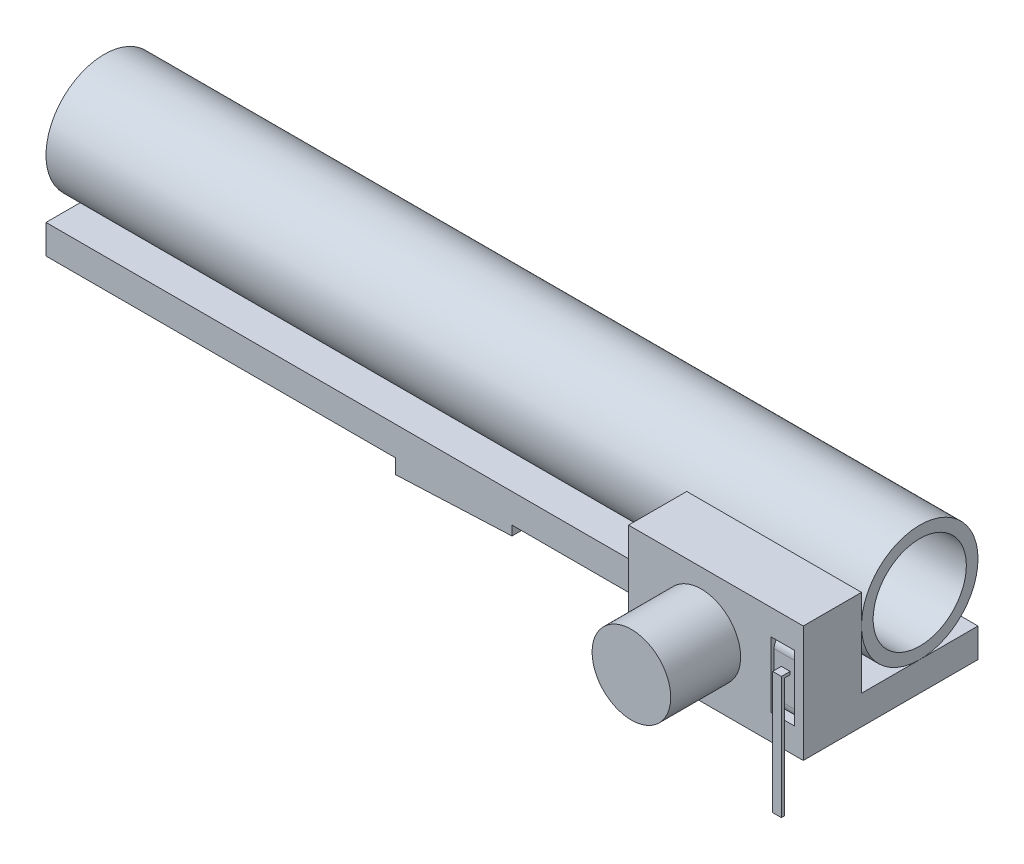
SolidWorks part; units mm, degrees
ref_plane "Front Plane" through (0, 0, 0) normal (0, 0, 1) x (1, 0, 0)
ref_plane "Top Plane" through (0, 0, 0) normal (0, 1, 0) x (1, 0, 0)
ref_plane "Right Plane" through (0, 0, 0) normal (1, 0, 0) x (0, 0, -1)
sketch "Sketch2" plane through (0, 0, 0) normal (1, 0, 0) x (0, 0, -1)
  line L0 (-25.4, 25.4) -> (-25.4, -25.4) construction
  line L1 (-25.4, -25.4) -> (25.4, -25.4) construction
  line L2 (25.4, -25.4) -> (25.4, 25.4) construction
  line L3 (25.4, 25.4) -> (-25.4, 25.4) construction
  point P2 (25.4, 0)
  point P5 (0, 25.4)
  dimension "D1" = 50.8
ref_plane "Plane1" through (0, 0, 0) normal (1, 0, 0) x (0, 0, -1)
sketch "Sketch3" plane through (0, 0, 0) normal (1, 0, 0) x (0, 0, -1)
  circle A0 centre (0, 0) radius 25.4
  dimension "D1" = 50.8
extrude "Boss-Extrude1" add sketch "Sketch3" against normal blind 355.6
shell "Shell1" thickness 5.08 removed face at (0, 0, -25.4)
sketch "Sketch4" plane through (0, 0, 0) normal (0, 0, 1) x (1, 0, 0)
  line L0 (-355.6, -25.4) -> (0, -25.4)
  line L2 (0, -27.94) -> (0, 27.94) construction
  line L3 (-355.6, -25.4) -> (0, -25.4) construction
  line L4 (-355.6, -25.4) -> (-355.6, -38.1)
  line L5 (-355.6, -38.1) -> (0, -38.1)
  line L6 (0, -38.1) -> (0, -25.4)
  dimension "D1" = 12.7
extrude "Boss-Extrude2" add sketch "Sketch4" along normal blind 25.4 and the other way blind 25.4 separate body
sketch "Sketch5" plane through (0, 0, 25.4) normal (0, 0, 1) x (1, 0, 0)
  line L1 (0, -38.1) -> (-76.2, -38.1)
  line L2 (0, -38.1) -> (0, 12.7)
  line L3 (0, 12.7) -> (-76.2, 12.7)
  line L4 (-76.2, -38.1) -> (-76.2, 12.7)
  line L8 (-355.6, -38.1) -> (0, -38.1) construction
  line L9 (0, -38.1) -> (0, -25.4) construction
  dimension "D1" = 76.2
  dimension "D2" = 50.8
extrude "Boss-Extrude3" add sketch "Sketch5" along normal blind 25.4
sketch "Sketch6" plane through (0, 0, 50.8) normal (0, 0, 1) x (1, 0, 0)
  line L1 (-3.81, -26.9875) -> (-13.97, -26.9875)
  line L2 (-3.81, -26.9875) -> (-3.81, 1.5875)
  line L3 (-3.81, 1.5875) -> (-13.97, 1.5875)
  line L4 (-13.97, -26.9875) -> (-13.97, 1.5875)
  line L5 (-3.81, 1.5875) -> (-3.81, 12.7) construction
  line L6 (0, 12.7) -> (-76.2, 12.7) construction
  line L7 (0, -38.1) -> (0, 12.7) construction
  line L8 (-3.81, -26.9875) -> (-3.81, -38.1) construction
  line L9 (-76.2, -38.1) -> (0, -38.1) construction
  dimension "D1" = 28.575
  dimension "D2" = 10.16
  dimension "D3" = 3.81
extrude "Cut-Extrude1" cut sketch "Sketch6" against normal blind 19.05
sketch "Sketch7" plane through (-13.97, 0, 0) normal (1, 0, 0) x (0, 0, -1)
  line L0 (-31.75, 1.5875) -> (-31.75, -26.9875) construction
  line L1 (-44.45, -26.9875) -> (-36.83, -26.9875)
  line L2 (-49.53, -21.9075) -> (-49.53, -3.4925)
  line L3 (-44.45, 1.5875) -> (-36.83, 1.5875)
  line L4 (-31.75, -21.9075) -> (-31.75, -3.4925)
  line L5 (-31.75, 1.5875) -> (-50.8, 1.5875) construction
  line L6 (-50.8, 1.5875) -> (-50.8, -26.9875) construction
  line L7 (-31.75, -26.9875) -> (-50.8, -26.9875) construction
  arc A0 (-36.83, -26.9875) -> (-31.75, -21.9075) centre (-36.83, -21.9075) ccw
  arc A1 (-44.45, -26.9875) -> (-49.53, -21.9075) centre (-44.45, -21.9075) cw
  arc A2 (-36.83, 1.5875) -> (-31.75, -3.4925) centre (-36.83, -3.4925) cw
  arc A3 (-49.53, -3.4925) -> (-44.45, 1.5875) centre (-44.45, -3.4925) cw
  point P14 (-50.8, -26.9875)
  dimension "D1" = 5.08
  dimension "D2" = 1.27
extrude "Boss-Extrude4" add sketch "Sketch7" along normal up to next
sketch "Sketch8" plane through (0, 0, 49.53) normal (0, 0, 1) x (1, 0, 0)
  line L0 (-3.81, -3.4925) -> (-13.97, -3.4925) construction
  line L1 (-10.795, -8.5725) -> (-6.985, -8.5725)
  line L2 (-10.795, -8.5725) -> (-10.795, -9.8425)
  line L3 (-10.795, -9.8425) -> (-6.985, -9.8425)
  line L4 (-6.985, -8.5725) -> (-6.985, -9.8425)
  point P6 (-8.89, -8.5725)
  point P7 (-8.89, -3.4925)
  dimension "D1" = 5.08
  dimension "D2" = 1.27
  dimension "D3" = 3.81
extrude "Boss-Extrude5" add sketch "Sketch8" along normal blind 2.54
sketch "Sketch10" plane through (0, 0, 52.07) normal (0, 0, 1) x (1, 0, 0)
  line L0 (-3.81, 1.5875) -> (-13.97, 1.5875) construction
  line L1 (-10.795, -8.5725) -> (-6.985, -8.5725)
  line L2 (-10.795, -8.5725) -> (-10.795, -61.9125)
  line L3 (-10.795, -61.9125) -> (-6.985, -61.9125)
  line L4 (-6.985, -8.5725) -> (-6.985, -61.9125)
  line L5 (-6.985, -9.8425) -> (-6.985, -8.5725) construction
  dimension "D1" = 63.5
extrude "Boss-Extrude6" add sketch "Sketch10" along normal blind 1.27
sketch "Sketch11" plane through (0, 0, 50.8) normal (0, 0, 1) x (1, 0, 0)
  line L0 (0, 12.7) -> (-76.2, 12.7) construction
  line L1 (-76.2, 12.7) -> (-76.2, -38.1) construction
  circle A0 centre (-44.45, -12.7) radius 17.145
  dimension "D1" = 34.29
  dimension "D2" = 25.4
  dimension "D3" = 31.75
extrude "Boss-Extrude7" add sketch "Sketch11" along normal blind 30.48
sketch "Sketch12" plane through (0, 0, 0) normal (0, 0, 1) x (1, 0, 0)
  line L1 (-203.1516, -44.45) -> (-152.4, -42.2341)
  line L3 (-203.1516, -44.45) -> (-203.1516, -38.1)
  line L4 (-203.1516, -38.1) -> (-152.4, -38.1)
  line L5 (-152.4, -38.1) -> (-152.4, -42.2341)
  line L6 (0, -38.1) -> (0, 12.7) construction
  line L7 (-355.6, -38.1) -> (-76.2, -38.1) construction
  point P1 (-198.606, -44.45)
  point P9 (-152.4, -46.4192)
  point P10 (-152.4, -41.1034)
  dimension "D1" = 50.8
  dimension "D2" = 2.5
  dimension "D3" = 6.35
  dimension "D4" = 152.4
extrude "Boss-Extrude8" add sketch "Sketch12" along normal up to vertex (25.4 mm away) and the other way up to vertex (25.4 mm away) up to point (-76.2, -38.1, 25.4) other way up to point (0, -38.1, -25.4)
